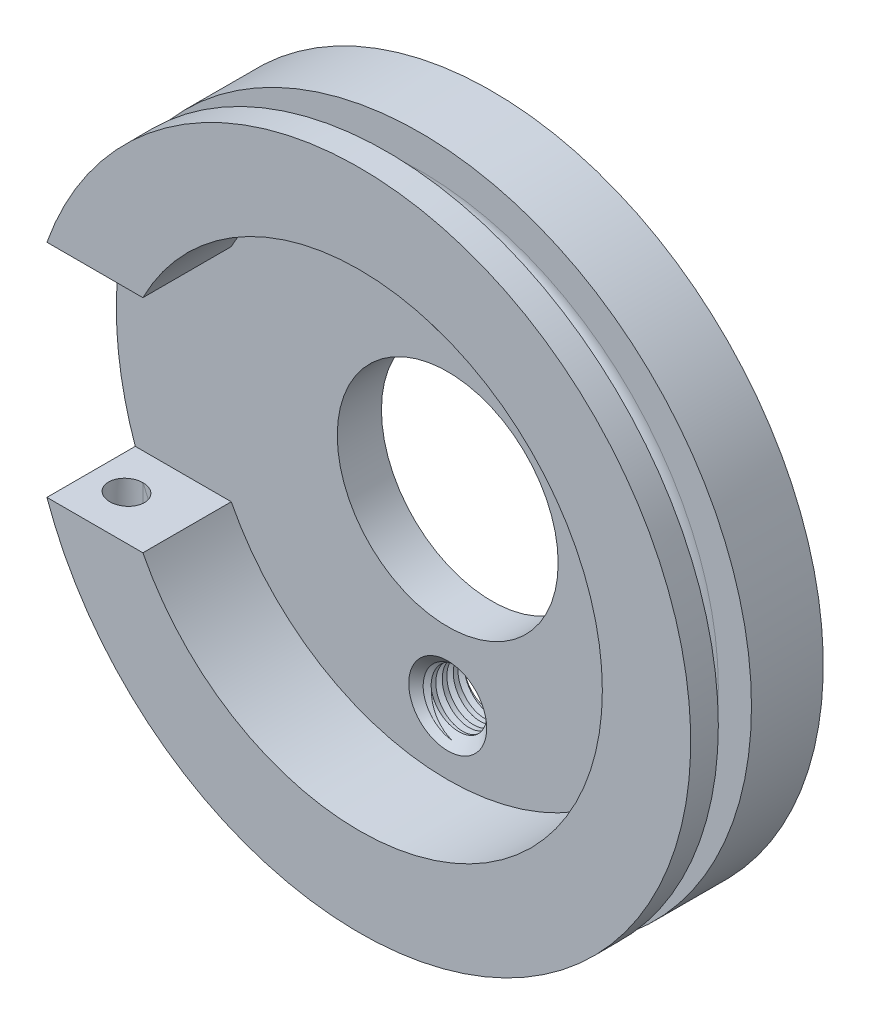
SolidWorks part; units mm, degrees
ref_plane "Front Plane" through (0, 0, 0) normal (0, 0, 1) x (1, 0, 0)
ref_plane "Top Plane" through (0, 0, 0) normal (0, 1, 0) x (1, 0, 0)
ref_plane "Right Plane" through (0, 0, 0) normal (1, 0, 0) x (0, 0, -1)
sketch "Sketch1" plane through (0, 0, 0) normal (0, 0, 1) x (1, 0, 0)
  circle A0 centre (0, 0) radius 11
  circle A1 centre (0, 0) radius 5
  dimension "D1" = 22
  dimension "D2" = 10
extrude "Boss-Extrude1" add sketch "Sketch1" along normal blind 2
sketch "Sketch3" plane through (0, 0, 0) normal (0, 0, -1) x (-1, 0, 0)
  circle A1 centre (0, 0) radius 11 construction
  circle A2 centre (0, 0) radius 15
  circle A3 centre (0, 0) radius 15
  circle A4 centre (0, 0) radius 11
  dimension "D1" = 4
extrude "Boss-Extrude2" add sketch "Sketch3" against normal blind 6
sketch "Sketch4" plane through (0, 0, 2) normal (0, 0, 1) x (1, 0, 0)
  line L0 (0, -15) -> (0, 15) construction
  circle A0 centre (0, 0) radius 15 construction
  point P7 (0, 0)
sketch "Sketch7" plane through (0, 0, 2) normal (0, 0, 1) x (1, 0, 0)
  line L0 (0, 0) -> (-7.3001, 0) construction
  circle A0 centre (0, 8.1) radius 1.2648
  circle A1 centre (0, -8.1) radius 1.2648
extrude "Cut-Extrude2" cut sketch "Sketch7" against normal through all
sketch "Sketch8" plane through (0, 0, 6) normal (0, 0, 1) x (1, 0, 0)
  line L0 (0, 0) -> (-15, 0) construction
  line L2 (-20.5, -5) -> (-9.5, -5)
  line L3 (-20.5, -5) -> (-20.5, 5)
  line L4 (-20.5, 5) -> (-9.5, 5)
  line L5 (-9.5, -5) -> (-9.5, 5)
  line L6 (-20.5, -5) -> (-9.5, 5) construction
  line L7 (-20.5, 5) -> (-9.5, -5) construction
  circle A0 centre (0, 0) radius 15 construction
  dimension "D1" = 10
  dimension "D2" = 11
sketch "Sketch12" plane through (0, 0, 0) normal (0, 1, 0) x (1, 0, 0)
  line L0 (-15, -2) -> (-12, -2) construction
  line L1 (-15, 0) -> (-15, -6) construction
  line L2 (-15, -6) -> (15, -6) construction
  line L3 (-13.5, -2) -> (-13.5, -6) construction
  line L4 (-20.5, -6) -> (-9.5, -6) construction
  line L5 (-13.5, -4.75) -> (-15, -4.75)
  line L6 (-13.5, -3.25) -> (-15, -3.25)
  line L7 (-15, -4.75) -> (-15, -3.25)
  line L8 (0, 0) -> (0, -10.4219) construction
  arc A0 (-13.5, -4.75) -> (-13.5, -3.25) centre (-13.5, -4) ccw
  dimension "D3" = 1.5
  dimension "D1" = 3
  dimension "D2" = 4
revolve "Cut-Revolve2" cut sketch "Sketch12" angle 360 about L8
extrude "Cut-Extrude4" cut sketch "Sketch8" against normal up to surface (4 mm away) up to face at (1.2648, 8.1, 2)
sketch "Sketch13" plane through (0, -5, 0) normal (0, 1, 0) x (1, 0, 0)
  line L0 (-12.5399, -3.25) -> (-12.5399, -4.75) construction
  line L1 (-14.1421, -4.75) -> (-14.1421, -3.25)
  line L2 (-14.1421, -3.25) -> (-12.5399, -3.25)
  line L3 (-14.1421, -4.75) -> (-12.5399, -4.75)
  spline S0 degree 3 poles (1857.0574, 703.0372) (-81.4236, 52.523) (-17.0091, -9.0019) (-11.9027, -4.4734) (-11.8391, -4.3901) (-11.7525, -4.206) (-11.7289, -4.104) (-11.7285, -3.8987) (-11.7516, -3.7966) (-11.8383, -3.611) (-11.9017, -3.5277) (-17.0974, 1.0927) (-82.2417, -63.2519) (1858.4022, -707.1019) knots -8.030505 -8.030505 -8.030505 -8.030505 0.25 0.25 0.375 0.375 0.5 0.5 0.625 0.625 0.75 0.75 9.151163 9.151163 9.151163 9.151163 only from (-12.5399, -4.75) to (-12.5399, -3.25) construction
  spline S1 degree 3 poles (-12.5399, -4.75) (-12.3366, -4.75) (-12.1306, -4.6755) (-11.9027, -4.4734) (-11.8391, -4.3901) (-11.7525, -4.206) (-11.7289, -4.104) (-11.7285, -3.8987) (-11.7516, -3.7966) (-11.8383, -3.611) (-11.9017, -3.5277) (-12.1302, -3.3245) (-12.3357, -3.25) (-12.5399, -3.25) knots 0 0 0 0 0.25 0.25 0.375 0.375 0.5 0.5 0.625 0.625 0.75 0.75 1 1 1 1
  spline S2 degree 3 poles (-12.5399, -4.75) (-12.7433, -4.75) (-12.9493, -4.6755) (-13.1771, -4.4734) (-13.2408, -4.3901) (-13.3274, -4.206) (-13.351, -4.104) (-13.3514, -3.8987) (-13.3282, -3.7966) (-13.2416, -3.611) (-13.1782, -3.5277) (-12.9497, -3.3245) (-12.7442, -3.25) (-12.5399, -3.25) knots 0 0 0 0 0.25 0.25 0.375 0.375 0.5 0.5 0.625 0.625 0.75 0.75 1 1 1 1
  line M7 (-14.1421, -3.25) -> (-12.5399, -3.25)
  line M9 (-12.5399, -4.75) -> (-14.1421, -4.75)
extrude "Boss-Extrude3" add sketch "Sketch13" against normal blind 5 contours S2 L1 M9 M7 region at (-13.6421, -5, 4)
sketch "Sketch14" plane through (0, 0, 6) normal (0, 0, 1) x (1, 0, 0)
  line L2 (-14.1421, -5) -> (-14.1421, -10)
  line L3 (-14.1421, -10) -> (-12.5399, -10)
  line L4 (-14.1421, -5) -> (-14.1421, -10)
  line L5 (-14.1421, -10) -> (-12.5399, -10)
  line L7 (-12.5399, -10) -> (-12.5399, -8.231)
  line L8 (-12.5399, -10) -> (-12.5399, -8.231)
  arc A1 (-14.1421, -5) -> (-12.5399, -8.231) centre (0, 0) ccw
  arc A2 (-14.1421, -5) -> (-12.5399, -8.231) centre (0, 0) ccw
  dimension "D1" = 0
sketch "Sketch15" plane through (0, 0, 4.75) normal (0, 0, 1) x (1, 0, 0)
  line L3 (-14.1421, -5) -> (-14.1421, -10)
  line L4 (-14.1421, -10) -> (-12.5399, -10)
  line L5 (-12.5399, -10) -> (-12.5399, -8.231)
  line L6 (-14.1421, -5) -> (-14.1421, -10)
  line L7 (-14.1421, -10) -> (-12.5399, -10)
  line L8 (-12.5399, -10) -> (-12.5399, -8.231)
  arc A1 (-14.1421, -5) -> (-12.5399, -8.231) centre (0, 0) ccw
  arc A2 (-14.1421, -5) -> (-12.5399, -8.231) centre (0, 0) ccw
  dimension "D1" = 0
extrude "Cut-Extrude6" cut sketch "Sketch15" against normal through all
mirror "Mirror2" about plane through (0, 0, 0) normal (0, 1, 0) of "Cut-Extrude6", "Boss-Extrude3"
sketch "Sketch16" plane through (0, 0, 2) normal (0, 0, 1) x (1, 0, 0)
  circle A0 centre (0, -8.1) radius 1.2648 construction
  circle A1 centre (0, -8.1) radius 1.2648
curve "Helix/Spiral1" pitch 0.5 height 5 radius 1.2648 centre (0, -8.1, 2) axis (0, 0, -1) start towards (0, 1, 0)
chamfer "Chamfer1" distance 0.5 angle 45 1 edges at (-1.2648, -8.1, 2)
sketch "Sketch17" plane through (0, 0, 0) normal (1, 0, 0) x (0, 0, -1)
  line L0 (-2, -6.8352) -> (-2, -6.5852) construction
  line L1 (-2, -6.5852) -> (-2.2165, -6.9602)
  line L2 (-2.2165, -6.9602) -> (-1.7835, -6.9602)
  line L3 (-1.7835, -6.9602) -> (-2, -6.5852)
  circle A0 centre (-2, -6.8352) radius 0.125 construction
  dimension "D1" = 0.25
sweep "Cut-Sweep1" cut profiles "Sketch17" path "Helix/Spiral1" align with end faces yes
sketch "Sketch18" plane through (0, 0, 2) normal (0, 0, 1) x (1, 0, 0)
  circle A0 centre (0, 8.1) radius 1.2648 construction
  circle A1 centre (0, 8.1) radius 1.2648
curve "Helix/Spiral2" pitch 0.5 height 5 radius 1.2648 centre (0, 8.1, 2) axis (0, 0, -1) start towards (0, 1, 0)
chamfer "Chamfer2" distance 0.5 angle 45 1 edges at (1.2648, 8.1, 2)
sketch "Sketch19" plane through (0, 0, 0) normal (1, 0, 0) x (0, 0, -1)
  line L0 (-1.5, 9.3648) -> (-1.5, 9.6148) construction
  line L1 (-1.5, 9.6148) -> (-1.7165, 9.2398)
  line L2 (-1.7165, 9.2398) -> (-1.2835, 9.2398)
  line L3 (-1.2835, 9.2398) -> (-1.5, 9.6148)
  circle A0 centre (-1.5, 9.3648) radius 0.125 construction
  dimension "D1" = 0.25
sweep "Cut-Sweep2" cut profiles "Sketch19" path "Helix/Spiral2" align with end faces yes
